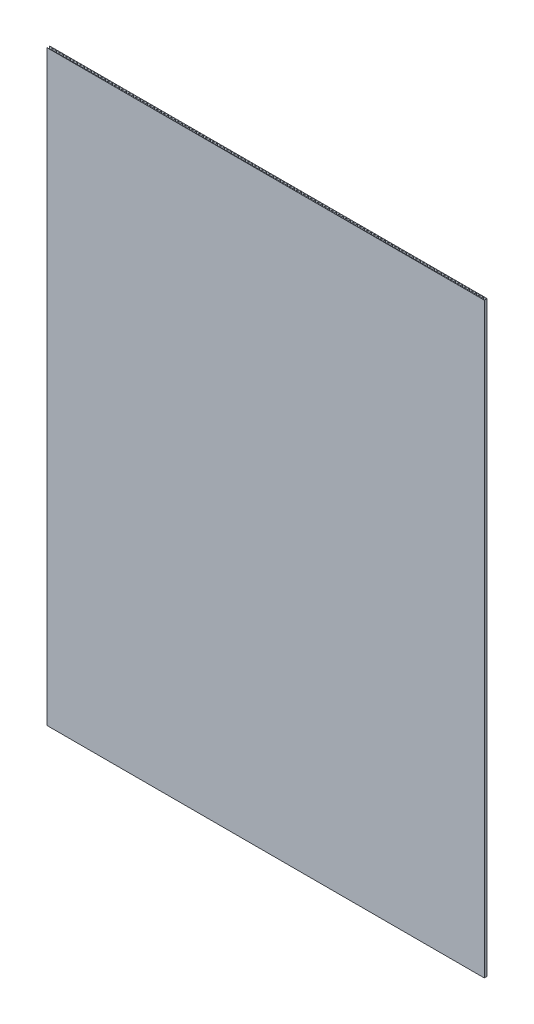
SolidWorks part; units mm, degrees
material "Acrylic (Medium-high impact)"
ref_plane "Front Plane" through (0, 0, 0) normal (0, 0, 1) x (1, 0, 0)
ref_plane "Top Plane" through (0, 0, 0) normal (0, 1, 0) x (1, 0, 0)
ref_plane "Right Plane" through (0, 0, 0) normal (1, 0, 0) x (0, 0, -1)
sketch "Sketch1" plane through (0, 0, 0) normal (0, 1, 0) x (1, 0, 0)
  line L0 (5, -4) -> (-5.3, -4)
  line L1 (-5.3, -4) -> (5, -4) construction
  line L2 (-5, -4) -> (-5, 4) construction
  line L3 (-5.3, 4) -> (5, 4) construction
  line L4 (5, -4) -> (5, 4) construction
  line L5 (-5, -4) -> (5, 4) construction
  line L6 (-5, 4) -> (5, -4) construction
  line L7 (4.7, -3.7) -> (4.7, 3.7)
  line L8 (-5.3, 3.7) -> (4.7, 3.7)
  line L9 (-5.3, -3.7) -> (4.7, -3.7)
  line L10 (5, 4) -> (5, -4)
  line L11 (-5, 4) -> (5, 4) construction
  line L12 (-5, 3.7) -> (5, 3.7) construction
  line L13 (-5, -3.7) -> (5, -3.7) construction
  line L14 (-5, -4) -> (5, -4) construction
  line L15 (5, 4) -> (-5.3, 4)
  line L16 (-5.3, 4) -> (-5.3, -4) construction
  line L17 (-5.3, 4) -> (-5.3, 3.7)
  line L18 (4.7, -4) -> (4.7, 4) construction
  line L19 (-5.3, -3.7) -> (-5.3, -4)
  point P0 (0, 0)
  dimension "D1" = 8
  dimension "D2" = 10
  dimension "D6" = 0.3
  dimension "D3" = 0.3
  dimension "D4" = 0.3
  dimension "D5" = 0.3
extrude "Boss-Extrude1" add sketch "Sketch1" along normal blind 1678
pattern_linear "LPattern1" count 125 spacing 10 along (1, 0, 0) of "Boss-Extrude1"
